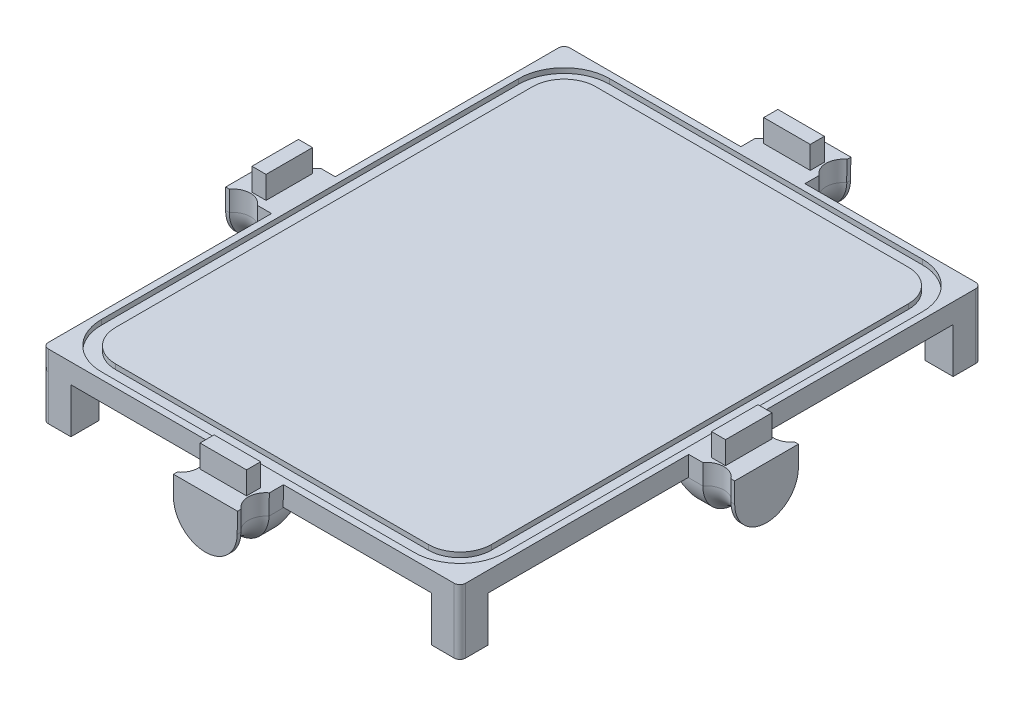
SolidWorks part; units mm, degrees
ref_plane "Front Plane" through (0, 0, 0) normal (0, 0, 1) x (1, 0, 0)
ref_plane "Top Plane" through (0, 0, 0) normal (0, 1, 0) x (1, 0, 0)
ref_plane "Right Plane" through (0, 0, 0) normal (1, 0, 0) x (0, 0, -1)
sketch "Sketch1" plane through (0, 0, 0) normal (0, 1, 0) x (1, 0, 0)
  line L1 (-39.4255, 34.2673) -> (54.5545, 34.2673)
  line L2 (-39.4255, 34.2673) -> (-39.4255, -83.1942)
  line L3 (-39.4255, -83.1942) -> (54.5545, -83.1942)
  line L4 (54.5545, 34.2673) -> (54.5545, -83.1942)
  dimension "D1" = 93.98
  dimension "D2" = 117.4615
extrude "Boss-Extrude1" add sketch "Sketch1" along normal blind 4.445
sketch "Sketch2" plane through (0, 4.445, 0) normal (0, 1, 0) x (1, 0, 0)
  line L0 (-33.8692, 28.711) -> (-33.8692, 34.2673)
  line L1 (-27.5192, 28.711) -> (42.6483, 28.711)
  line L2 (-33.8692, 22.361) -> (-33.8692, -71.288)
  line L3 (-27.5192, -77.638) -> (42.6483, -77.638)
  line L4 (48.9983, 22.361) -> (48.9983, -71.288)
  line L5 (54.5545, 34.2673) -> (-39.4255, 34.2673) construction
  line L6 (-33.8692, 28.711) -> (-39.4255, 28.711)
  line L7 (-39.4255, 34.2673) -> (-39.4255, -83.1942) construction
  line L8 (48.9983, -77.638) -> (54.5545, -77.638)
  line L9 (54.5545, -83.1942) -> (54.5545, 34.2673) construction
  line L10 (54.5545, -77.638) -> (48.9983, -77.638)
  line L11 (48.9983, -77.638) -> (48.9983, -83.1942)
  line L12 (-39.4255, -83.1942) -> (54.5545, -83.1942) construction
  arc A0 (42.6483, -77.638) -> (48.9983, -71.288) centre (42.6483, -71.288) ccw
  arc A1 (-33.8692, -71.288) -> (-27.5192, -77.638) centre (-27.5192, -71.288) ccw
  arc A2 (48.9983, 22.361) -> (42.6483, 28.711) centre (42.6483, 22.361) ccw
  arc A3 (-27.5192, 28.711) -> (-33.8692, 22.361) centre (-27.5192, 22.361) ccw
  dimension "D5" = 6.35
  dimension "D1" = 5.5562
  dimension "D2" = 5.5562
  dimension "D3" = 5.5562
  dimension "D4" = 5.5562
sketch "Sketch3" plane through (0, 4.445, 0) normal (0, 1, 0) x (1, 0, 0)
  line L0 (-36.0917, 30.9335) -> (-39.4255, 34.2673) construction
  line L1 (-32.8716, 30.9335) -> (48.0006, 30.9335)
  line L2 (-36.0917, 27.7134) -> (-36.0917, -76.6404)
  line L3 (7.5645, 34.2673) -> (7.5645, -83.1942) construction
  line L4 (-36.0917, 30.9335) -> (-36.0917, -76.6404) construction
  line L5 (-36.0917, -79.8605) -> (-36.0008, -79.8605) construction
  line L6 (51.2208, -79.8605) -> (51.2208, -79.7696) construction
  line L7 (51.2208, 30.9335) -> (51.1299, 30.9335) construction
  line L8 (-37.3617, -81.1305) -> (52.4908, -81.1305)
  line L9 (52.4908, -81.1305) -> (52.4908, 32.2035)
  line L10 (51.1299, -79.8605) -> (51.2208, -79.8605) construction
  line L11 (54.5545, 34.2673) -> (-39.4255, 34.2673) construction
  line L12 (-39.4255, -83.1942) -> (54.5545, -83.1942) construction
  line L13 (54.5545, -24.4635) -> (-39.4255, -24.4635) construction
  line L14 (-34.028, -77.7967) -> (49.157, -77.7967)
  line L15 (49.157, -77.7967) -> (49.157, 28.8698)
  line L16 (49.157, 28.8698) -> (-34.028, 28.8698)
  line L17 (-34.028, 28.8698) -> (-34.028, -77.7967)
  line L18 (-34.028, -77.7967) -> (49.157, -77.7967)
  line L19 (49.157, -77.7967) -> (49.157, 28.8698)
  line L20 (49.157, 28.8698) -> (-34.028, 28.8698)
  line L21 (-34.028, 28.8698) -> (-34.028, -77.7967)
  line L22 (54.5545, -83.1942) -> (54.5545, 34.2673) construction
  line L23 (-39.4255, 34.2673) -> (-39.4255, -83.1942) construction
  line L24 (-37.3617, -76.6404) -> (-37.3617, 27.7134)
  line L25 (48.0006, -81.1305) -> (-32.8716, -81.1305)
  line L26 (52.4908, 27.7134) -> (52.4908, -76.6404)
  line L27 (48.0006, 32.2035) -> (-32.8716, 32.2035)
  line L28 (52.4908, 32.2035) -> (-37.3617, 32.2035)
  line L29 (-37.3617, 32.2035) -> (-37.3617, -81.1305)
  line L30 (-37.3617, -81.1305) -> (52.4908, -81.1305) construction
  line L31 (52.4908, -81.1305) -> (52.4908, 32.2035) construction
  line L32 (52.4908, 32.2035) -> (-32.8716, 32.2035) construction
  line L33 (-37.3617, 27.7134) -> (-37.3617, -81.1305) construction
  line L34 (-36.0917, 30.9335) -> (-32.8716, 27.7134) construction
  line L35 (-32.8716, 27.7134) -> (-32.8716, 32.2035) construction
  line L36 (-32.8716, 27.7134) -> (-37.3617, 27.7134) construction
  line L37 (51.1299, 30.9335) -> (51.2208, 30.9335) construction
  line L38 (48.0006, 30.9335) -> (-36.0917, 30.9335) construction
  line L39 (51.2208, 30.9335) -> (-36.0917, 30.9335) construction
  line L40 (51.2208, 30.8426) -> (51.2208, 30.9335) construction
  line L41 (51.2208, -79.8605) -> (51.2208, 30.9335) construction
  line L42 (-36.0917, -79.8605) -> (51.2208, -79.8605) construction
  line L43 (51.2208, -76.6404) -> (51.2208, 27.7134)
  line L44 (-36.0917, -79.7696) -> (-36.0917, -79.8605) construction
  line L45 (-36.0917, -79.7696) -> (-36.0917, -79.8605) construction
  line L46 (-36.0917, 30.9335) -> (-36.0917, -79.8605) construction
  line L47 (-32.8716, -79.8605) -> (48.0006, -79.8605)
  arc A0 (-36.0917, 27.7134) -> (-32.8716, 30.9335) centre (-32.8716, 27.7134) cw
  arc A1 (-37.3617, 27.7134) -> (-32.8716, 32.2035) centre (-32.8716, 27.7134) cw
  arc A2 (51.2208, 27.7134) -> (48.0006, 30.9335) centre (48.0006, 27.7134) ccw
  arc A3 (52.4908, 27.7134) -> (48.0006, 32.2035) centre (48.0006, 27.7134) ccw
  arc A4 (51.2208, -76.6404) -> (48.0006, -79.8605) centre (48.0006, -76.6404) cw
  arc A5 (52.4908, -76.6404) -> (48.0006, -81.1305) centre (48.0006, -76.6404) cw
  arc A6 (-36.0917, -76.6404) -> (-32.8716, -79.8605) centre (-32.8716, -76.6404) ccw
  arc A7 (-37.3617, -76.6404) -> (-32.8716, -81.1305) centre (-32.8716, -76.6404) ccw
  dimension "D4" = 6.35
  dimension "D1" = 5.3975
  dimension "D2" = 2.0638
  dimension "D3" = 2.0638
sketch "Sketch7" plane through (-39.4255, 0, 0) normal (-1, 0, 0) x (0, 0, 1)
  line L0 (24.4635, 4.445) -> (24.4635, -0.127) construction
  line L1 (-34.2673, 4.445) -> (83.1942, 4.445) construction
  line L2 (17.288, -0.127) -> (31.639, -0.127) construction
  line L3 (31.639, -0.127) -> (31.639, 4.445)
  line L4 (17.288, -0.127) -> (17.288, 4.445)
  line L5 (31.639, 4.445) -> (17.288, 4.445)
  arc A0 (31.639, -0.127) -> (17.288, -0.127) centre (24.4635, -0.127) cw
  line M4 (-34.2673, 0) -> (83.1942, 0)
  line M6 (83.1942, 4.445) -> (-34.2673, 4.445)
  dimension "D1" = 7.1755
  dimension "D2" = 4.572
extrude "Boss-Extrude2" add sketch "Sketch7" along normal blind 10.3505 contours A0 M4 | A0 L3 L4 M6 M4 region at (-39.4255, -3.1039, 24.4635) region at (-39.4255, 2.2225, 24.4635)
sketch "Sketch8" plane through (0, 4.445, 0) normal (0, 1, 0) x (1, 0, 0)
  line L0 (-39.4255, -31.639) -> (-39.4255, -17.288)
  line L1 (-39.4255, -24.4635) -> (-45.7755, -24.4635) construction
  line L2 (-45.7755, -24.4635) -> (-45.7755, -17.288) construction
  line L3 (-49.776, -17.288) -> (-39.4255, -17.288) construction
  line L4 (-45.7755, -24.4635) -> (-45.7755, -31.639) construction
  line L5 (-49.776, -31.639) -> (-39.4255, -31.639) construction
  line L6 (-45.7755, -31.639) -> (-48.9505, -31.639)
  line L7 (-45.7755, -31.639) -> (-42.6005, -31.639)
  line L8 (-45.7755, -17.288) -> (-48.9505, -17.288)
  line L9 (-45.7755, -17.288) -> (-42.6005, -17.288)
  line L10 (-45.7755, -17.288) -> (-45.7755, -18.8755) construction
  line L11 (-45.7755, -18.8755) -> (-49.776, -18.8755) construction
  line L12 (-49.776, -31.639) -> (-49.776, -17.288) construction
  line L13 (-45.7755, -18.8755) -> (-39.4255, -18.8755) construction
  line L14 (-45.7755, -31.639) -> (-45.7755, -30.0515) construction
  line L15 (-45.7755, -30.0515) -> (-49.776, -30.0515) construction
  line L16 (-45.7755, -30.0515) -> (-39.4255, -30.0515) construction
  arc A0 (-42.6005, -17.288) -> (-48.9505, -17.288) centre (-45.7755, -14.9067) cw
  arc A1 (-42.6005, -31.639) -> (-48.9505, -31.639) centre (-45.7755, -34.0202) ccw
  line M7 (-39.4255, -17.288) -> (-49.776, -17.288)
  line M9 (-49.776, -31.639) -> (-39.4255, -31.639)
  dimension "D1" = 6.35
  dimension "D2" = 3.175
  dimension "D3" = 3.175
  dimension "D4" = 3.175
  dimension "D5" = 3.175
  dimension "D6" = 1.5875
  dimension "D7" = 1.5875
extrude "Cut-Extrude3" cut sketch "Sketch8" against normal blind 4.572 contours A1 M9 | A0 M7 region at (-45.7755, 4.445, 17.9353) region at (-45.7755, 4.445, 30.9916)
sketch "Sketch9" plane through (0, -0.127, 0) normal (0, 1, 0) x (1, 0, 0)
  line L0 (-45.7755, -31.639) -> (-45.7755, -24.4635) construction
  line L1 (-48.9505, -31.639) -> (-42.6005, -31.639) construction
  line L4 (-45.7755, -24.4635) -> (-46.0295, -24.4635) construction
  line L6 (-48.9505, -31.639) -> (-48.9505, -30.0515) construction
  line L7 (-48.9505, -30.0515) -> (-45.7755, -30.0515) construction
  line L9 (-45.7755, -30.0515) -> (-42.6005, -30.0515) construction
  line L12 (-42.6005, -30.0515) -> (-42.6005, -31.639) construction
  line L13 (-42.6005, -31.639) -> (-48.9505, -31.639)
  arc A0 (-42.6005, -31.639) -> (-48.9505, -31.639) centre (-45.7755, -34.0202) ccw
  arc A2 (-42.6005, -31.639) -> (-48.9505, -31.639) centre (-45.7755, -34.0202) ccw construction
  dimension "D1" = 7.1755
  dimension "D2" = 0.254
revolve "Cut-Revolve2" cut sketch "Sketch9" angle 180 about L4 region at (-45.7755, -0.127, 30.9916) reverse direction yes
sketch "Sketch17" plane through (0, 4.445, 0) normal (0, 1, 0) x (1, 0, 0)
  line L0 (-39.4255, -31.639) -> (-39.4255, -17.288) construction
  line L1 (-42.6005, -31.639) -> (-42.6005, -17.288) construction
  line L2 (-42.6005, -24.4635) -> (-42.6005, -29.7022)
  line L3 (-42.6005, -29.7022) -> (-45.7755, -29.7022)
  line L4 (-45.7755, -29.7022) -> (-45.7755, -24.4635)
  line L5 (-45.7755, -24.4635) -> (-45.7755, -19.2247)
  line L6 (-45.7755, -24.4635) -> (-42.6005, -24.4635) construction
  line L7 (-45.7755, -19.2247) -> (-42.6005, -19.2247)
  line L8 (-42.6005, -19.2247) -> (-42.6005, -24.4635)
  dimension "D1" = 5.2387
  dimension "D2" = 3.175
  dimension "D3" = 5.2387
  dimension "D4" = 5.2387
extrude "Boss-Extrude3" add sketch "Sketch17" along normal blind 5.08
ref_plane "Plane1" through (7.5645, 0, 0) normal (-1, 0, 0) x (0, 0, 1)
ref_plane "Plane2" through (-14.3199, 0, 14.3199) normal (-0.7071, 0, 0.7071) x (0.7071, 0, 0.7071)
mirror "Mirror1" about plane through (7.5645, 0, 0) normal (-1, 0, 0) of "Boss-Extrude2", "Cut-Extrude3", "Cut-Revolve2", "Boss-Extrude3"
ref_plane "Plane3" through (21.8844, 0, 21.8844) normal (0.7071, 0, 0.7071) x (0.7071, 0, -0.7071)
sketch "Sketch18" plane through (0, 0, 83.1942) normal (0, 0, 1) x (1, 0, 0)
  line L0 (-39.4255, 4.445) -> (54.5545, 4.445) construction
  line L2 (-39.4255, 0) -> (54.5545, 0) construction
  line L5 (14.7389, -0.1263) -> (14.8194, 4.445)
  line L6 (0.389, 0) -> (0.389, 4.445)
  line L7 (14.8194, 4.445) -> (0.389, 4.445)
  line L8 (54.5545, 4.445) -> (54.5545, 0) construction
  arc A0 (14.7389, -0.1263) -> (0.389, 0) centre (7.5645, 0) cw
  dimension "D2" = 7.1755
  dimension "D3" = 46.99
  dimension "D1" = 4.572
  dimension "D4" = 46.99
extrude "Boss-Extrude4" add sketch "Sketch18" along normal blind 10.3505
sketch "Sketch19" plane through (0, 4.445, 0) normal (0, 1, 0) x (1, 0, 0)
  line L0 (14.8194, -83.1942) -> (0.389, -83.1942) construction
  line L1 (7.6042, -83.1942) -> (7.6042, -89.5442) construction
  line L2 (7.6042, -89.5442) -> (0.389, -89.5442) construction
  line L3 (0.389, -93.5447) -> (0.389, -83.1942) construction
  line L4 (7.6042, -89.5442) -> (14.8194, -89.5442) construction
  line L5 (14.8194, -93.5447) -> (14.8194, -83.1942) construction
  line L6 (0.389, -89.5442) -> (0.389, -92.7192)
  line L7 (0.389, -89.5442) -> (0.389, -86.3692)
  line L8 (0.389, -89.5442) -> (1.9765, -89.5442) construction
  line L9 (1.9765, -89.5442) -> (1.9765, -93.5447) construction
  line L10 (14.8194, -93.5447) -> (0.389, -93.5447) construction
  line L11 (1.9765, -89.5442) -> (1.9765, -83.1942) construction
  line L12 (14.8194, -89.5442) -> (14.8194, -86.3692)
  line L13 (14.8194, -89.5442) -> (14.8194, -92.7192)
  arc A0 (0.389, -92.7192) -> (0.389, -86.3692) centre (-1.9922, -89.5442) ccw
  arc A1 (14.8194, -92.7192) -> (14.8194, -86.3692) centre (17.2006, -89.5442) cw
  dimension "D1" = 6.35
  dimension "D2" = 3.175
  dimension "D3" = 3.175
  dimension "D4" = 1.5875
extrude "Cut-Extrude4" cut sketch "Sketch19" against normal blind 4.572 and the other way blind 10
sketch "Sketch20" plane through (0, -0.127, 0) normal (0, 1, 0) x (1, 0, 0)
  line L0 (0.389, -92.7192) -> (0.389, -86.3692)
  line L1 (0.389, -89.5442) -> (1.9765, -89.5442) construction
  line L2 (1.9765, -89.5442) -> (1.9765, -92.7192) construction
  line L3 (1.9765, -89.5442) -> (1.9765, -86.3692) construction
  line L4 (0.389, -89.5442) -> (7.5645, -89.5442) construction
  line L5 (7.5645, -89.5442) -> (7.5645, -89.7982) construction
  arc A0 (0.3901, -92.7184) -> (0.3901, -86.3701) centre (-1.9922, -89.5442) ccw construction
  arc A1 (0.389, -92.7192) -> (0.389, -86.3692) centre (-1.9922, -89.5442) ccw
  dimension "D1" = 7.1755
  dimension "D2" = 0.254
revolve "Cut-Revolve3" cut sketch "Sketch20" angle 180 about L5
sketch "Sketch23" plane through (0, 4.445, 0) normal (0, 1, 0) x (1, 0, 0)
  line L0 (14.8194, -86.3692) -> (0.389, -86.3692) construction
  line L1 (7.6042, -86.3692) -> (7.6042, -89.5442) construction
  line L2 (12.8429, -89.5442) -> (2.3654, -89.5442)
  line L3 (2.3654, -89.5442) -> (2.3654, -86.3692)
  line L4 (2.3654, -86.3692) -> (12.8429, -86.3692)
  line L5 (12.8429, -89.5442) -> (12.8429, -86.3692)
  dimension "D1" = 3.175
  dimension "D2" = 5.2387
extrude "Boss-Extrude5" add sketch "Sketch23" along normal blind 5.08
ref_plane "Plane4" through (0, 0, 24.4635) normal (0, 0, 1) x (1, 0, 0)
fillet "Fillet4" radius 1.27 4 edges at (-39.4255, 2.2225, -34.2673) (-39.4255, 2.2225, 83.1942) (54.5545, 2.2225, 83.1942) (54.5545, 2.2225, -34.2673)
mirror "Mirror2" about plane through (0, 0, 24.4635) normal (0, 0, 1) of "Boss-Extrude4", "Cut-Extrude4", "Cut-Revolve3", "Boss-Extrude5"
fillet "Fillet6" radius 7.112 4 edges at (7.5651, 0, -34.2673) (54.5545, 0, 24.4635) (-39.4255, 0, 24.4635) (7.5651, 0, 83.1942)
sketch "Sketch24" plane through (0, 4.445, 0) normal (0, 1, 0) x (1, 0, 0)
  line L4 (14.8194, 32.7592) -> (0.389, 32.7592)
  line L5 (-37.9174, -17.288) -> (-37.9174, -31.639)
  line L6 (-37.9174, 32.7592) -> (-37.9174, -17.288)
  line L7 (0.389, 32.7592) -> (-37.9174, 32.7592)
  line L8 (-37.9174, 22.5198) -> (-37.9174, -17.288)
  line L9 (0.389, 32.7592) -> (-27.678, 32.7592)
  line L10 (0.389, -81.6861) -> (14.8194, -81.6861)
  line L11 (53.0464, -31.639) -> (53.0464, -17.288)
  line L24 (42.807, 29.6159) -> (14.8194, 29.6159)
  line L25 (14.8194, 29.6159) -> (0.389, 29.6159)
  line L26 (0.389, 29.6159) -> (-27.678, 29.6159)
  line L27 (-34.7741, 22.5198) -> (-34.7741, -17.288)
  line L28 (-34.7741, -17.288) -> (-34.7741, -31.639)
  line L29 (53.0464, 32.7592) -> (14.8194, 32.7592)
  line L30 (53.0464, -17.288) -> (53.0464, 32.7592)
  line L31 (42.807, 32.7592) -> (14.8194, 32.7592)
  line L32 (53.0464, -17.288) -> (53.0464, 22.5198)
  line L33 (-34.7741, -31.639) -> (-34.7741, -71.4467)
  line L34 (-27.678, -78.5429) -> (0.389, -78.5429)
  line L35 (0.389, -78.5429) -> (14.8194, -78.5429)
  line L36 (14.8194, -78.5429) -> (42.807, -78.5429)
  line L37 (14.8194, -81.6861) -> (53.0464, -81.6861)
  line L38 (53.0464, -81.6861) -> (53.0464, -31.639)
  line L39 (14.8194, -81.6861) -> (42.807, -81.6861)
  line L40 (53.0464, -71.4467) -> (53.0464, -31.639)
  line L41 (49.9031, -71.4467) -> (49.9031, -31.639)
  line L42 (49.9031, -31.639) -> (49.9031, -17.288)
  line L45 (-37.9174, -31.639) -> (-37.9174, -81.6861)
  line L46 (-37.9174, -81.6861) -> (0.389, -81.6861)
  line L47 (-37.9174, -31.639) -> (-37.9174, -71.4467)
  line L48 (-27.678, -81.6861) -> (0.389, -81.6861)
  line L76 (49.9031, -17.288) -> (49.9031, 22.5198)
  arc A2 (53.0464, 22.5198) -> (42.807, 32.7592) centre (42.807, 22.5198) ccw
  arc A3 (-27.678, 32.7592) -> (-37.9174, 22.5198) centre (-27.678, 22.5198) ccw
  arc A4 (-37.9174, -71.4467) -> (-27.678, -81.6861) centre (-27.678, -71.4467) ccw
  arc A5 (42.807, -81.6861) -> (53.0464, -71.4467) centre (42.807, -71.4467) ccw
  arc A6 (49.9031, 22.5198) -> (42.807, 29.6159) centre (42.807, 22.5198) ccw
  arc A7 (-27.678, 29.6159) -> (-34.7741, 22.5198) centre (-27.678, 22.5198) ccw
  arc A8 (-34.7741, -71.4467) -> (-27.678, -78.5429) centre (-27.678, -71.4467) ccw
  arc A9 (42.807, -78.5429) -> (49.9031, -71.4467) centre (42.807, -71.4467) ccw
  dimension "D6" = 10.2394
  dimension "D7" = 10.2394
  dimension "D1" = 1.5081
  dimension "D2" = 1.5081
  dimension "D3" = 1.5081
  dimension "D4" = 1.5081
  dimension "D5" = 3.1432
extrude "Cut-Extrude5" cut sketch "Sketch24" against normal blind 1.1112
sketch "Sketch25" plane through (0, 0, 0) normal (0, -1, 0) x (1, 0, 0)
  line L0 (54.5545, -32.9973) -> (54.5545, -27.9173)
  line L1 (54.5545, 17.288) -> (54.5545, -32.9973) construction
  line L2 (54.5545, -27.9173) -> (48.2045, -27.9173)
  line L3 (48.2045, -27.9173) -> (48.2045, -34.2673)
  line L4 (53.2845, -34.2673) -> (14.7411, -34.2673) construction
  line L7 (54.5545, 31.639) -> (54.5545, 17.288) construction
  line L8 (54.5545, 24.4635) -> (-39.4255, 24.4635) construction
  line L9 (0.389, 83.1942) -> (14.7411, 83.1942) construction
  line L10 (7.5651, 83.1942) -> (7.5651, -34.2673) construction
  line L11 (53.2845, -34.2673) -> (48.2045, -34.2673)
  line L12 (54.5545, 81.9242) -> (54.5545, 76.8442)
  line L13 (54.5545, 76.8442) -> (48.2045, 76.8442)
  line L14 (48.2045, 76.8442) -> (48.2045, 83.1942)
  line L15 (53.2845, 83.1942) -> (48.2045, 83.1942)
  line L16 (-38.1544, 83.1942) -> (-33.0744, 83.1942)
  line L17 (-33.0744, 76.8442) -> (-33.0744, 83.1942)
  line L18 (-39.4244, 76.8442) -> (-33.0744, 76.8442)
  line L19 (-39.4244, 81.9242) -> (-39.4244, 76.8442)
  line L20 (-39.4244, -32.9973) -> (-39.4244, -27.9173)
  line L21 (-39.4244, -27.9173) -> (-33.0744, -27.9173)
  line L22 (-33.0744, -27.9173) -> (-33.0744, -34.2673)
  line L23 (-38.1544, -34.2673) -> (-33.0744, -34.2673)
  arc A0 (53.2845, -34.2673) -> (54.5545, -32.9973) centre (53.2845, -32.9973) ccw
  arc A1 (53.2845, -34.2673) -> (54.5545, -32.9973) centre (53.2845, -32.9973) ccw construction
  arc A2 (53.2845, 83.1942) -> (54.5545, 81.9242) centre (53.2845, 81.9242) cw
  arc A3 (-38.1544, 83.1942) -> (-39.4244, 81.9242) centre (-38.1544, 81.9242) ccw
  arc A4 (-38.1544, -34.2673) -> (-39.4244, -32.9973) centre (-38.1544, -32.9973) cw
  dimension "D1" = 6.35
  dimension "D2" = 6.35
extrude "Boss-Extrude6" add sketch "Sketch25" along normal blind 10.16
ref_plane "Plane5" through (0, -22.6053, -13.6364) normal (0, -0.8563, -0.5165) x (1, 0, 0)
sketch "Sketch26" plane through (0, -22.6053, -13.6364) normal (0, -0.8563, -0.5165) x (1, 0, 0)
  line L0 (-38.1544, -24.094) -> (53.2845, -24.094)
  line L1 (53.2845, -24.094) -> (63.1981, -24.094)
